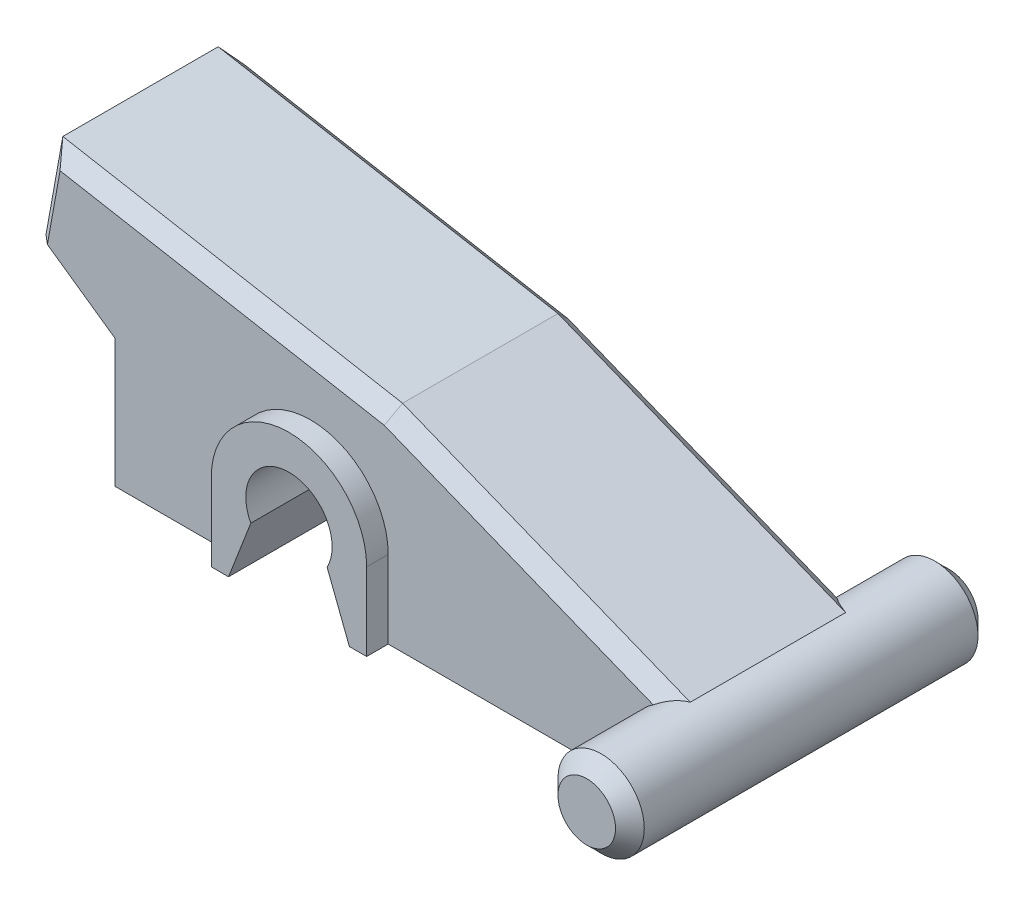
SolidWorks part; units mm, degrees
ref_plane "Front Plane" through (0, 0, 0) normal (0, 0, 1) x (1, 0, 0)
ref_plane "Top Plane" through (0, 0, 0) normal (0, 1, 0) x (1, 0, 0)
ref_plane "Right Plane" through (0, 0, 0) normal (1, 0, 0) x (0, 0, -1)
sketch "Sketch1" plane through (0, 0, 0) normal (0, 0, 1) x (1, 0, 0)
  line L0 (10, -4.4) -> (10, -1.4)
  line L1 (-10, -4.4) -> (10, -4.4)
  line L2 (-10, -4.4) -> (-10, 4.4)
  line L3 (-10, 4.4) -> (10, 4.4)
  line L4 (10, -4.4) -> (10, 4.4)
  line L5 (-10, -4.4) -> (10, 4.4) construction
  line L6 (-10, 4.4) -> (10, -4.4) construction
  line L7 (10, -1.4) -> (0, 2.6)
  line L8 (0, 2.6) -> (-11.8102, 4.7258)
  line L9 (-11.8102, 4.7258) -> (-12.3948, 1.478)
  line L10 (-12.3948, 1.478) -> (-10, -0.2)
  point P0 (0, 0)
  dimension "D1" = 20
  dimension "D2" = 8.8
  dimension "D3" = 3
  dimension "D4" = 7
  dimension "D5" = 10
  dimension "D6" = 12
  dimension "D7" = 3.3
  dimension "D8" = 4.2
extrude "Boss-Extrude1" add sketch "Sketch1" along normal mid plane 6.4 contours L7 L8 L2 L1 L0 | L9 L10 L2 L8 region at (-1.4987, -0.9499, 0) region at (-11.0126, 2.476, 0)
sketch "Sketch2" plane through (0, 0, 3.2) normal (0, 0, 1) x (1, 0, 0)
  line L0 (-10, -4.4) -> (10, -4.4) construction
  line L1 (-10, -4.4) -> (-10, -0.2) construction
  line L2 (-5.4, -1.7) -> (-5.4, -4.4)
  line L3 (-5.4, -4.4) -> (-2.7, -4.4)
  line L4 (-2.7, -4.4) -> (-5.4, -1.7)
  line L5 (-2.7, -4.4) -> (0, -4.4)
  line L6 (0, -4.4) -> (0, -1.7)
  line L7 (0, -1.7) -> (-2.7, -4.4)
  circle A0 centre (-2.7, -1.7) radius 2.7
  line M13 (-10, -4.4) -> (10, -4.4)
  dimension "D1" = 5.4
  dimension "D2" = 7.3
extrude "Boss-Extrude2" add sketch "Sketch2" along normal mid plane 1.5 contours L7 A0 L4 | L4 A0 | L7 A0 | A0 L6 M13 | A0 L2 M13 region at (-4.7969, -3.7969, 3.2) region at (-2.7, -1.3499, 3.2) region at (-4.2767, -3.2767, 3.2) region at (-0.6031, -3.7969, 3.2) region at (-1.1233, -3.2767, 3.2)
mirror "Mirror1" about plane through (0, 0, 0) normal (0, 0, 1) of "Boss-Extrude2"
sketch "Sketch3" plane through (0, 0, 3.95) normal (0, 0, 1) x (1, 0, 0)
  line L0 (-4.8, -4.4) -> (-0.6, -4.4)
  line L1 (-5.4, -4.4) -> (0, -4.4) construction
  line L2 (-4.8, -4.4) -> (-4.0266, -2.4)
  line L3 (-4.0266, -2.4) -> (-1.3734, -2.4)
  line L4 (-1.3734, -2.4) -> (-0.6, -4.4)
  circle A0 centre (-2.7, -1.7) radius 1.5
  point P8 (-2.7, -4.4)
  line M5 (-5.4, -4.4) -> (0, -4.4)
  dimension "D1" = 3
  dimension "D2" = 4.2
  dimension "D3" = 0
  dimension "D4" = 2
extrude "Cut-Extrude1" cut sketch "Sketch3" against normal through all both and the other way through all contours L3 A0 | A0 L2 L4 M5 | L4 L0 L2 L3 region at (-2.7, -3.6868, 3.95) region at (-2.7, -1.4198, 3.95)
sketch "Sketch4" plane through (0, 0, 0) normal (0, 0, 1) x (1, 0, 0)
  line L0 (10, -4.4) -> (10, -1.4) construction
  circle A0 centre (10, -2.9) radius 1.5
extrude "Boss-Extrude3" add sketch "Sketch4" along normal mid plane 12.6
chamfer "Chamfer1" distance 0.5 angle 45 2 edges at (11.5, -2.9, -6.3) (11.5, -2.9, 6.3)
chamfer "Chamfer2" distance 0.5 angle 45 10 edges at (-10, -2.3, 3.2) (-11.1974, 0.639, 3.2) (-12.1025, 3.1019, 3.2) (-5.9051, 3.6629, 3.2) (5, 0.6, 3.2) (-10, -2.3, -3.2) (-11.1974, 0.639, -3.2) (-12.1025, 3.1019, -3.2) (-5.9051, 3.6629, -3.2) (5, 0.6, -3.2)
sketch "Sketch5" plane through (0, 0, 3.2) normal (0, 0, 1) x (1, 0, 0)
  line L0 (-10.5291, 2.2466) -> (-10.4382, 2.7516)
  line L1 (-10.4382, 2.7516) -> (-0.4711, 0.9575)
  line L2 (-0.4711, 0.9575) -> (7.3953, -2.1891)
  line L3 (7.3167, -3.2) -> (0, -3.2)
  line L4 (0, -1.7) -> (0, -4.4) construction
  line L5 (-10.5291, 2.2466) -> (-8.3, 0.6846)
  line L6 (-8.3, 0.6846) -> (-8.3, -3.2)
  line L7 (-8.3, -3.2) -> (-5.4, -3.2)
  line L8 (-5.4, -4.4) -> (-5.4, -1.7) construction
  line L9 (-11.4067, 4.1452) -> (-11.8461, 1.7041) construction
  line L10 (-0.1386, 2.1169) -> (-11.4067, 4.1452) construction
  line L11 (9.2123, -1.6234) -> (-0.1386, 2.1169) construction
  line L12 (0, -4.4) -> (10, -4.4) construction
  line L15 (-9.5, -4.4) -> (-5.4, -4.4) construction
  line L16 (-9.5, 0.0602) -> (-9.5, -4.4) construction
  line L17 (-11.8461, 1.7041) -> (-9.5, 0.0602) construction
  line L18 (-5.4, -3.2) -> (-5.4, -1.7)
  line L19 (0, -3.2) -> (0, -1.7)
  circle A0 centre (10, -2.9) radius 2.7
  circle A1 centre (10, -2.9) radius 1.5 construction
  circle A2 centre (-2.7, -1.7) radius 2.7
  line M14 (-5.4, -4.4) -> (-5.4, -1.7)
  arc M15 (-5.4, -1.7) -> (0, -1.7) centre (-2.7, -1.7) cw
  line M16 (0, -1.7) -> (0, -4.4)
  dimension "D4" = 1.2
  dimension "D9" = 5.4
  dimension "D1" = 1.2
  dimension "D2" = 1.2
  dimension "D3" = 1.2
  dimension "D5" = 1.2
  dimension "D6" = 1.2
  dimension "D7" = 1.2
  dimension "D8" = 1.2
extrude "Cut-Extrude2" cut sketch "Sketch5" against normal offset from surface (5.2 mm away) 1.2 contours A0 L2 L1 L0 L5 L6 L7 L3 M14 M15 M16 region at (-10.2978, 2.4656, 3.2) up to face at (-3.1844, -1.1086, -3.2)
mirror "Mirror2" about plane through (0, 0, 3.2) normal (0, 0, 1) of bodies 107
delete or keep bodies "-1" type delete bodies bodies 107
